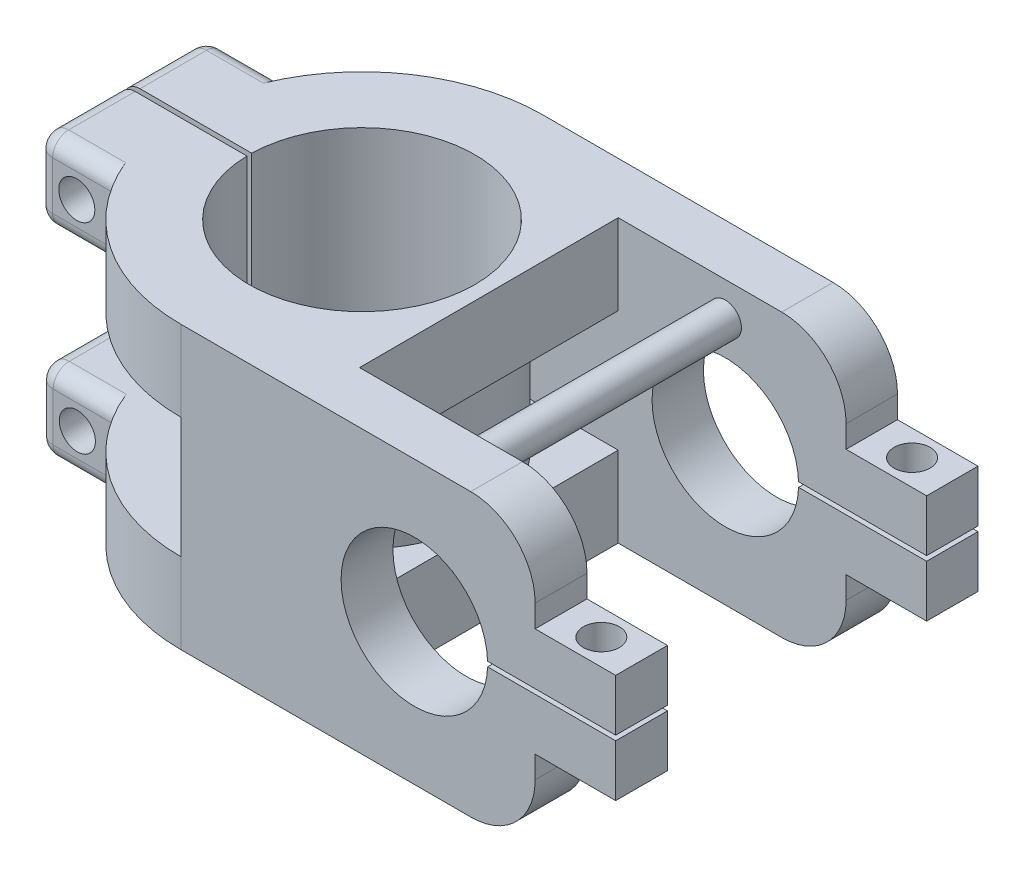
SolidWorks part; units mm, degrees
ref_plane "Front Plane" through (0, 0, 0) normal (0, 0, 1) x (1, 0, 0)
ref_plane "Top Plane" through (0, 0, 0) normal (0, 1, 0) x (1, 0, 0)
ref_plane "Right Plane" through (0, 0, 0) normal (1, 0, 0) x (0, 0, -1)
sketch "Sketch2" plane through (0, 0, 0) normal (0, 1, 0) x (1, 0, 0)
  circle A0 centre (0, 0) radius 17.78
  circle A2 centre (0, 0) radius 28.575
  dimension "D1" = 35.56
  dimension "D2" = 57.15
extrude "Boss-Extrude3" add sketch "Sketch2" along normal blind 12.7
sketch "Sketch3" plane through (0, 12.7, 0) normal (0, 1, 0) x (1, 0, 0)
  line L0 (0, 0) -> (20.2056, -20.2056) construction
  line L1 (0, 0) -> (20.2056, 20.2056) construction
  line L2 (0, 0) -> (-28.575, 0) construction
  line L3 (-25.3321, 0) -> (-25.3321, 13.2218) construction
  line L4 (-25.3321, 13.2218) -> (-25.3321, -13.2218)
  line L5 (-25.3321, 13.2218) -> (-36.1866, 13.2218)
  line L6 (-36.1866, 13.2218) -> (-36.1866, -13.2218)
  line L7 (-36.1866, -13.2218) -> (-25.3321, -13.2218)
  circle A0 centre (0, 0) radius 28.575 construction
extrude "Cut-Extrude1" cut sketch "Sketch3" against normal blind 12.7
sketch "Sketch4" plane through (0, 12.7, 0) normal (0, 1, 0) x (1, 0, 0)
  line L0 (0, 0) -> (-25.3321, 0) construction
  line L1 (-25.3321, -13.2218) -> (-25.3321, 13.2218) construction
  line L2 (-16.3768, 0) -> (-16.3768, 0.381)
  line L3 (-16.3768, 0) -> (-16.3768, -0.381)
  line L4 (-16.3768, 0.381) -> (-26.0036, 0.381)
  line L5 (-16.3768, -0.381) -> (-26.0036, -0.381)
  line L6 (-26.0036, -0.381) -> (-26.0036, 0.381)
  dimension "D1" = 0.762
extrude "Cut-Extrude2" cut sketch "Sketch4" against normal blind 12.7
sketch "Sketch5" plane through (-25.3321, 0, 0) normal (-1, 0, 0) x (0, 0, 1)
  line L1 (0.381, 12.7) -> (13.2218, 12.7)
  line L2 (0.381, 12.7) -> (0.381, 0)
  line L3 (0.381, 0) -> (13.2218, 0)
  line L4 (13.2218, 12.7) -> (13.2218, 0)
extrude "Boss-Extrude4" add sketch "Sketch5" along normal blind 12.7
sketch "Sketch6" plane through (-25.3321, 0, 0) normal (-1, 0, 0) x (0, 0, 1)
  line L1 (-13.2218, 12.7) -> (-0.381, 12.7)
  line L2 (-13.2218, 12.7) -> (-13.2218, 0)
  line L3 (-13.2218, 0) -> (-0.381, 0)
  line L4 (-0.381, 12.7) -> (-0.381, 0)
extrude "Boss-Extrude5" add sketch "Sketch6" along normal blind 12.7
sketch "Sketch7" plane through (0, 0, 13.2218) normal (0, 0, 1) x (1, 0, 0)
  line L0 (-31.6821, 12.7) -> (-31.6821, 0) construction
  line L1 (-38.0321, 12.7) -> (-25.3321, 12.7) construction
  line L2 (-38.0321, 0) -> (-25.3321, 0) construction
  circle A0 centre (-31.6821, 6.35) radius 2.8448
extrude "Cut-Extrude3" cut sketch "Sketch7" against normal blind 33.02
fillet "Fillet1" radius 2.54 1 edges at (-38.0321, 6.35, 13.2218)
fillet "Fillet2" radius 2.54 1 edges at (-38.0321, 6.35, -13.2218)
fillet "Fillet3" radius 2.54 3 edges at (-30.4121, 12.7, -13.2218) (-37.2882, 12.7, -12.4778) (-38.0321, 12.7, -5.5314)
fillet "Fillet4" radius 2.54 3 edges at (-30.4121, 12.7, 13.2218) (-37.2882, 12.7, 12.4778) (-38.0321, 12.7, 5.5314)
fillet "Fillet5" radius 2.54 3 edges at (-30.4121, 0, -13.2218) (-37.2882, 0, -12.4778) (-38.0321, 0, -5.5314)
fillet "Fillet6" radius 2.54 3 edges at (-30.4121, 0, 13.2218) (-37.2882, 0, 12.4778) (-38.0321, 0, 5.5314)
sketch "Sketch8" plane through (0, 12.7, 0) normal (0, 1, 0) x (1, 0, 0)
  circle A0 centre (0, 0) radius 18.7388
  circle A1 centre (0, 0) radius 17.78
extrude "Boss-Extrude6" add sketch "Sketch8" along normal blind 19.05
sketch "Sketch9" plane through (0, 31.75, 0) normal (0, 1, 0) x (1, 0, 0)
  circle A0 centre (0, 0) radius 28.575
extrude "Boss-Extrude7" add sketch "Sketch9" along normal blind 12.7
sketch "Sketch12" plane through (0, 44.45, 0) normal (0, 1, 0) x (1, 0, 0)
  line L0 (0, 0) -> (-28.575, 0) construction
  line L1 (-25.2365, 13.4034) -> (-25.2365, -13.4034)
  line L2 (-25.2365, 13.4034) -> (-36.6122, 13.4034)
  line L3 (-25.2365, -13.4034) -> (-36.6122, -13.4034)
  line L4 (-36.6122, -13.4034) -> (-36.6122, 13.4034)
  circle A0 centre (0, 0) radius 28.575 construction
extrude "Cut-Extrude4" cut sketch "Sketch12" against normal blind 12.7
sketch "Sketch13" plane through (-25.2365, 0, 0) normal (-1, 0, 0) x (0, 0, 1)
  line L0 (-18.7388, 31.75) -> (18.7388, 31.75) construction
  line L1 (-13.4034, 44.45) -> (13.4034, 44.45)
  line L2 (-13.4034, 44.45) -> (-13.4034, 31.75)
  line L3 (-13.4034, 31.75) -> (13.4034, 31.75)
  line L4 (13.4034, 44.45) -> (13.4034, 31.75)
  line L5 (13.4034, 31.75) -> (-13.4034, 31.75) construction
extrude "Boss-Extrude8" add sketch "Sketch13" along normal blind 12.7
sketch "Sketch14" plane through (0, 44.45, 0) normal (0, 1, 0) x (1, 0, 0)
  circle A0 centre (0, 0) radius 17.78
extrude "Cut-Extrude5" cut sketch "Sketch14" against normal blind 12.7
sketch "Sketch15" plane through (0, 44.45, 0) normal (0, 1, 0) x (1, 0, 0)
  line L0 (-37.9365, 0) -> (0, 0)
  line L1 (-37.9365, -13.4034) -> (-37.9365, 13.4034) construction
  line L2 (0, 0) -> (0, 0.381)
  line L3 (0, 0.381) -> (-38.0321, 0.381)
  line L4 (-38.0321, 0.381) -> (-37.9365, 0)
  line L5 (0, 0) -> (0, -0.381)
  line L6 (0, -0.381) -> (-37.9365, -0.381)
  line L7 (-37.9365, -0.381) -> (-37.9365, 0)
  line L8 (-37.9365, 0) -> (0, 0)
  circle M6 centre (0, 0) radius 17.78
  line M9 (-37.9365, 13.4034) -> (-37.9365, -13.4034)
  dimension "D1" = 0.381
extrude "Cut-Extrude6" cut sketch "Sketch15" against normal blind 12.7 contours L3 L0 M6 M9 region at (-27.8576, 44.45, -0.1905)
sketch "Sketch16" plane through (0, 44.45, 0) normal (0, 1, 0) x (1, 0, 0)
  line L6 (-37.9365, 0) -> (-16.9968, 0)
  line L7 (-37.9365, 0) -> (-37.9365, -0.381)
  line L8 (-37.9365, -0.381) -> (-16.9968, -0.381)
  line L9 (-16.9968, 0) -> (-16.9968, -0.381)
  dimension "D1" = 0.381
extrude "Cut-Extrude7" cut sketch "Sketch16" against normal blind 12.7
fillet "Fillet7" radius 2.54 1 edges at (-37.9365, 44.45, -6.8922)
fillet "Fillet8" radius 2.54 1 edges at (-37.9365, 44.45, 6.8922)
fillet "Fillet9" radius 2.54 1 edges at (-37.9365, 31.75, -6.8922)
fillet "Fillet10" radius 2.54 1 edges at (-37.9365, 31.75, 6.8922)
fillet "Fillet11" radius 2.54 5 edges at (-30.3165, 31.75, 13.4034) (-37.1925, 32.4939, 13.4034) (-30.3165, 44.45, 13.4034) (-37.1925, 43.7061, 13.4034) (-37.9365, 38.1, 13.4034)
fillet "Fillet12" radius 2.54 5 edges at (-30.3165, 44.45, -13.4034) (-37.1925, 43.7061, -13.4034) (-30.3165, 31.75, -13.4034) (-37.1925, 32.4939, -13.4034) (-37.9365, 38.1, -13.4034)
sketch "Sketch17" plane through (0, 0, 13.4034) normal (0, 0, 1) x (1, 0, 0)
  line L0 (-25.2365, 38.1) -> (-37.9365, 38.1) construction
  line L1 (-25.2365, 34.29) -> (-25.2365, 41.91) construction
  line L2 (-37.9365, 34.29) -> (-37.9365, 41.91) construction
  circle A0 centre (-31.5865, 38.1) radius 2.8448
extrude "Cut-Extrude8" cut sketch "Sketch17" against normal blind 29.464
sketch "Sketch19" plane through (0, 31.75, 0) normal (0, 1, 0) x (1, 0, 0)
  line L5 (-18.7349, 0.381) -> (-16.9078, 0.381)
  line L6 (-18.7349, 0.381) -> (-18.7349, -0.381)
  line L7 (-18.7349, -0.381) -> (-16.9078, -0.381)
  line L8 (-16.9078, 0.381) -> (-16.9078, -0.381)
extrude "Cut-Extrude13" cut sketch "Sketch19" against normal blind 29.464 body kept at (-35.3965, 31.75, -10.8634)
sketch "Sketch22" plane through (0, 12.7, 0) normal (0, 1, 0) x (1, 0, 0)
  line L0 (0, 0) -> (0, -18.7388) construction
  line L1 (0, -18.7388) -> (0, -20.3979) construction
  line L2 (0, -20.3979) -> (0, -28.575)
  line L3 (0, -28.575) -> (55.88, -28.575)
  line L4 (55.88, -28.575) -> (55.88, -20.3979)
  line L5 (55.88, -20.3979) -> (0, -20.3979)
  arc A0 (-18.7349, -0.381) -> (-18.7349, 0.381) centre (0, 0) ccw construction
  arc A1 (-26.5034, -10.6818) -> (-26.5034, 10.6818) centre (0, 0) ccw construction
  dimension "D1" = 55.88
extrude "Boss-Extrude12" add sketch "Sketch22" along normal blind 31.75 and the other way blind 12.7
sketch "Sketch23" plane through (0, 12.7, 0) normal (0, 1, 0) x (1, 0, 0)
  line L0 (0, -20.3979) -> (0, -18.6659) construction
  line L1 (0, 18.7388) -> (0, 20.4709) construction
  line L2 (0, 20.4709) -> (0, 28.575)
  line L3 (0, 28.575) -> (55.88, 28.575)
  line L4 (0, 20.4709) -> (55.88, 20.4709)
  line L5 (55.88, 20.4709) -> (55.88, 28.575)
  arc A0 (-18.7349, -0.381) -> (-18.7349, 0.381) centre (0, 0) ccw construction
  arc A1 (20.0114, -20.3979) -> (-26.5034, 10.6818) centre (0, 0) ccw construction
  dimension "D1" = 1.7321
  dimension "D2" = 55.88
extrude "Boss-Extrude13" add sketch "Sketch23" along normal blind 31.75 and the other way blind 12.7
sketch "Sketch24" plane through (0, 0, -28.575) normal (0, 0, -1) x (-1, 0, 0)
  line L0 (-17.78, 22.225) -> (-55.88, 22.225) construction
  line L2 (-17.78, 44.45) -> (-17.78, 0) construction
  line L3 (-55.88, 44.45) -> (0, 44.45) construction
  line L4 (-55.88, 0) -> (-55.88, 44.45) construction
  circle A0 centre (-36.83, 22.225) radius 11.557
extrude "Cut-Extrude14" cut sketch "Sketch24" against normal blind 67.31
fillet "Fillet13" radius 10.16 1 edges at (55.88, 44.45, 24.4865)
fillet "Fillet14" radius 10.16 1 edges at (55.88, 0, 24.4865)
fillet "Fillet15" radius 10.16 1 edges at (55.88, 44.45, -24.5229)
fillet "Fillet16" radius 10.16 1 edges at (55.88, 0, -24.5229)
sketch "Sketch25" plane through (0, 44.45, 0) normal (0, 1, 0) x (1, 0, 0)
  line L0 (28.575, 0.0522) -> (28.575, 20.4709)
  line L1 (19.9368, 20.4709) -> (45.72, 20.4709) construction
  line L2 (28.575, 20.4709) -> (19.9368, 20.4709)
  line L3 (19.9368, 20.4709) -> (20.0114, -20.3979)
  line L4 (20.0114, -20.3979) -> (28.575, -20.3979)
  line L5 (45.72, -20.3979) -> (20.0114, -20.3979) construction
  line L6 (28.575, -20.3979) -> (28.575, 0.0522)
  arc A0 (20.0114, -20.3979) -> (19.9368, 20.4709) centre (0, 0) ccw construction
extrude "Cut-Extrude15" cut sketch "Sketch25" against normal blind 67.31
sketch "Sketch26" plane through (0, 0, -20.4709) normal (0, 0, 1) x (1, 0, 0)
  line L0 (36.83, 33.782) -> (36.83, 44.45) construction
  line L1 (19.9368, 44.45) -> (45.72, 44.45) construction
  circle A0 centre (36.83, 22.225) radius 11.557 construction
  circle A1 centre (36.83, 39.116) radius 2.54
extrude "Boss-Extrude14" add sketch "Sketch26" along normal blind 43.434
sketch "Sketch27" plane through (0, 0, 28.575) normal (0, 0, 1) x (1, 0, 0)
  line L0 (48.387, 22.225) -> (55.88, 22.225) construction
  line L1 (55.88, 10.16) -> (55.88, 34.29) construction
  line L2 (57.8595, 22.225) -> (46.9704, 22.225)
  line L3 (46.9704, 22.225) -> (46.9704, 22.606)
  line L4 (46.9704, 22.606) -> (57.8595, 22.606)
  line L5 (57.8595, 22.606) -> (57.8595, 22.225)
  circle A0 centre (36.83, 22.225) radius 11.557 construction
  dimension "D1" = 0.381
extrude "Cut-Extrude16" cut sketch "Sketch27" against normal blind 64.516
sketch "Sketch28" plane through (0, 0, 28.575) normal (0, 0, 1) x (1, 0, 0)
  line L0 (47.571, 22.225) -> (56.4711, 22.225)
  line L1 (56.4711, 22.225) -> (56.4711, 21.844)
  line L2 (56.4711, 21.844) -> (47.571, 21.844)
  line L3 (47.571, 21.844) -> (47.571, 22.225)
  dimension "D1" = 0.381
extrude "Cut-Extrude17" cut sketch "Sketch28" against normal blind 64.516
sketch "Sketch29" plane through (55.88, 0, 0) normal (1, 0, 0) x (0, 0, -1)
  line L0 (-28.575, 22.606) -> (-20.3979, 22.606)
  line L1 (-20.3979, 22.606) -> (-20.3979, 30.7831)
  line L2 (-20.3979, 22.606) -> (-20.3979, 34.29) construction
  line L3 (-20.3979, 30.7831) -> (-28.575, 30.7831)
  line L4 (-28.575, 22.606) -> (-28.575, 34.29) construction
  line L5 (-28.575, 30.7831) -> (-28.575, 22.606)
  dimension "D1" = 8.1771
extrude "Boss-Extrude15" add sketch "Sketch29" along normal blind 12.7
sketch "Sketch30" plane through (55.88, 0, 0) normal (1, 0, 0) x (0, 0, -1)
  line L0 (-28.575, 21.844) -> (-20.3979, 21.844)
  line L1 (-20.3979, 21.844) -> (-20.3979, 13.6669)
  line L2 (-20.3979, 10.16) -> (-20.3979, 21.844) construction
  line L3 (-20.3979, 13.6669) -> (-28.575, 13.6669)
  line L4 (-28.575, 10.16) -> (-28.575, 21.844) construction
  line L5 (-28.575, 13.6669) -> (-28.575, 21.844)
extrude "Boss-Extrude16" add sketch "Sketch30" along normal blind 12.7
sketch "Sketch31" plane through (0, 30.7831, 0) normal (0, 1, 0) x (1, 0, 0)
  line L0 (62.23, -20.3979) -> (62.23, -28.575) construction
  line L1 (68.58, -20.3979) -> (55.88, -20.3979) construction
  line L2 (68.58, -28.575) -> (55.88, -28.575) construction
  circle A0 centre (62.23, -24.4865) radius 2.8448
extrude "Cut-Extrude18" cut sketch "Sketch31" against normal blind 22.098
sketch "Sketch34" plane through (55.88, 0, 0) normal (1, 0, 0) x (0, 0, -1)
  line L0 (28.575, 22.606) -> (28.575, 30.7831)
  line L1 (28.575, 22.606) -> (28.575, 34.29) construction
  line L2 (28.575, 30.7831) -> (20.4709, 30.7831)
  line L3 (20.4709, 22.606) -> (20.4709, 34.29) construction
  line L4 (20.4709, 30.7831) -> (20.4709, 22.606)
  line L5 (20.4709, 22.606) -> (28.575, 22.606)
extrude "Boss-Extrude17" add sketch "Sketch34" along normal blind 12.7
sketch "Sketch35" plane through (55.88, 0, 0) normal (1, 0, 0) x (0, 0, -1)
  line L0 (28.575, 21.844) -> (28.575, 13.6669)
  line L1 (28.575, 10.16) -> (28.575, 21.844) construction
  line L2 (28.575, 13.6669) -> (20.4709, 13.6669)
  line L3 (20.4709, 10.16) -> (20.4709, 21.844) construction
  line L4 (20.4709, 13.6669) -> (20.4709, 21.844)
  line L5 (20.4709, 21.844) -> (28.575, 21.844)
extrude "Boss-Extrude18" add sketch "Sketch35" along normal blind 12.7
sketch "Sketch36" plane through (0, 30.7831, 0) normal (0, 1, 0) x (1, 0, 0)
  line L0 (62.23, 28.575) -> (62.23, 20.4709) construction
  line L1 (68.58, 28.575) -> (55.88, 28.575) construction
  line L2 (68.58, 20.4709) -> (55.88, 20.4709) construction
  circle A0 centre (62.23, 24.5229) radius 2.8448
extrude "Cut-Extrude19" cut sketch "Sketch36" against normal blind 27.686
